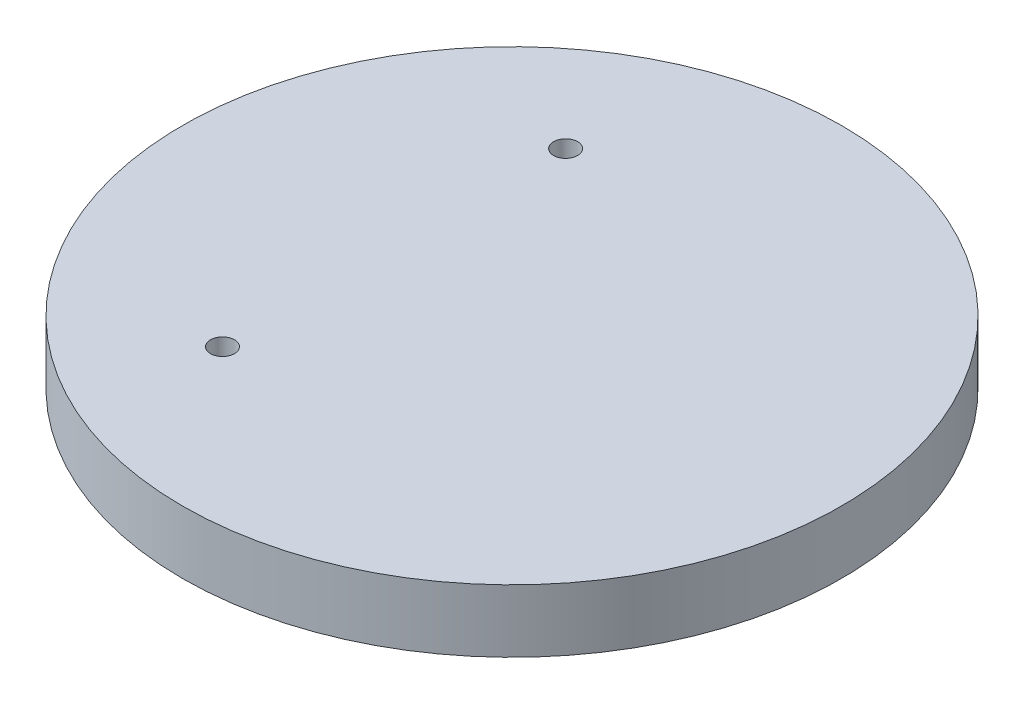
SolidWorks part; units mm, degrees
ref_plane "Front Plane" through (0, 0, 0) normal (0, 0, 1) x (1, 0, 0)
ref_plane "Top Plane" through (0, 0, 0) normal (0, 1, 0) x (1, 0, 0)
ref_plane "Right Plane" through (0, 0, 0) normal (1, 0, 0) x (0, 0, -1)
sketch "Sketch2" plane through (0, 0, 0) normal (0, 0, 1) x (1, 0, 0)
  line L0 (0, 0) -> (0, 6) construction
  line L1 (0, 4) -> (-2.43, 4)
  line L2 (-2.43, 3) -> (-2.43, 0)
  line L3 (-2.43, 0) -> (-4.43, 0)
  line L4 (-4.43, 0) -> (-4.43, 4)
  line L5 (-4.43, 4) -> (-29.5, 4)
  line L6 (-29.5, 4) -> (-29.5, 0)
  line L7 (-29.5, 0) -> (-31.5, 0)
  line L8 (-31.5, 0) -> (-31.5, 4)
  line L9 (-31.5, 4) -> (-31.5, 6)
  line L10 (-31.5, 6) -> (0, 6)
  line L11 (-2.43, 4) -> (-2.43, 3)
  line L12 (0, 6) -> (0, 4)
  point P13 (-4.43, 2)
  dimension "D1" = 6
  dimension "D2" = 31.5
  dimension "D3" = 2.43
  dimension "D4" = 2
  dimension "D5" = 2
  dimension "D6" = 4
  dimension "D7" = 6
  dimension "D8" = 2
  dimension "D9" = 2
revolve "Revolve1" add sketch "Sketch2" angle 360 about L0
fillet "Fillet1" radius 10 2 edges at (0, 4, -4.43) (0, 4, -29.5)
sketch "Sketch6" plane through (0, 6, 0) normal (0, 1, 0) x (1, 0, 0)
  line L0 (-22.55, -13.4) -> (0, -19.4)
  line L1 (-22.55, -11.4) -> (0, -11.4)
  line L2 (-22.55, -11.4) -> (-22.55, 11.4)
  line L3 (-22.55, 11.4) -> (0, 11.4)
  line L4 (0, -11.4) -> (0, 11.4)
  line L5 (-22.55, -11.4) -> (0, 11.4) construction
  line L6 (-22.55, 11.4) -> (0, -11.4) construction
  line L7 (-22.55, -11.4) -> (0, -11.4)
  line L8 (-22.55, -11.4) -> (-22.55, -19.4)
  line L9 (-22.55, -19.4) -> (0, -19.4)
  line L10 (0, -11.4) -> (0, -19.4)
  line L11 (-22.55, 11.4) -> (0, 11.4)
  line L12 (-22.55, 11.4) -> (-22.55, 19.4)
  line L13 (-22.55, 19.4) -> (0, 19.4)
  line L14 (0, 11.4) -> (0, 19.4)
  line L15 (-22.55, 11.4) -> (0, 11.4)
  line L16 (-22.55, 11.4) -> (-22.55, 13.4)
  line L17 (-22.55, 13.4) -> (0, 13.4)
  line L18 (0, 11.4) -> (0, 13.4)
  line L19 (-22.55, -11.4) -> (0, -11.4)
  line L20 (-22.55, -11.4) -> (-22.55, -13.4)
  line L21 (-22.55, -13.4) -> (0, -13.4)
  line L22 (0, -11.4) -> (0, -13.4)
  line L23 (-22.55, -19.4) -> (0, -13.4)
  line L24 (-22.55, 19.4) -> (0, 13.4)
  line L25 (-22.55, 13.4) -> (0, 19.4)
  circle A0 centre (-11.275, 16.4) radius 1.15
  circle A1 centre (-11.275, -16.4) radius 1.15
  point P0 (-11.275, 0)
  dimension "D1" = 22.8
  dimension "D2" = 22.55
  dimension "D3" = 0
  dimension "D4" = 11.4
  dimension "D5" = 8
  dimension "D6" = 8
  dimension "D7" = 2
  dimension "D8" = 2
extrude "Cut-Extrude1" cut sketch "Sketch6" against normal blind 10 contours A1 | A0
